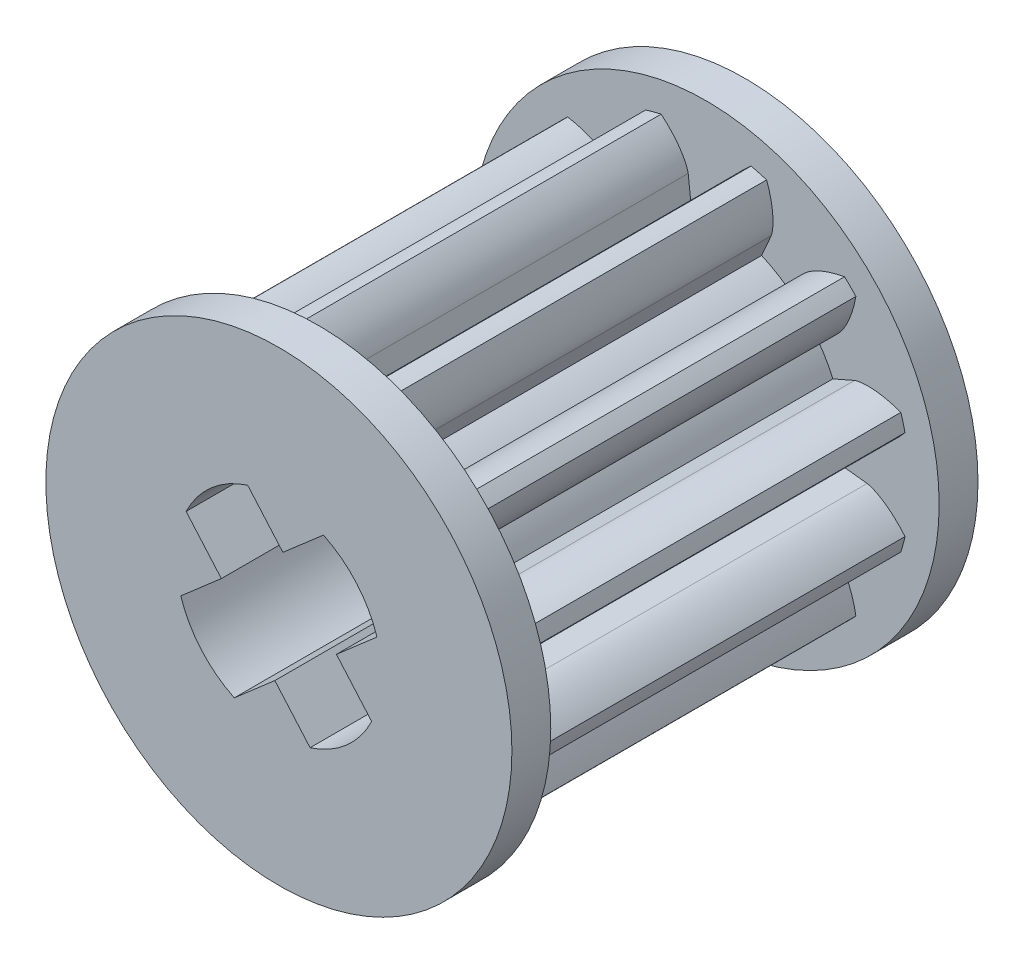
SolidWorks part; units mm, degrees
ref_plane "Front Plane" through (0, 0, 0) normal (0, 0, 1) x (1, 0, 0)
ref_plane "Top Plane" through (0, 0, 0) normal (0, 1, 0) x (1, 0, 0)
ref_plane "Right Plane" through (0, 0, 0) normal (1, 0, 0) x (0, 0, -1)
ref_axis "Axis1" [suppressed] through (0, 0, 71.2135) along (0, 0, -1)
sketch "Sketch1" plane through (0, 0, 0) normal (0, 0, 1) x (1, 0, 0)
  circle A0 centre (0, 0) radius 3.5625
  circle A1 centre (0, 0) radius 4.1723
  circle A2 centre (0, 0) radius 3.75
  circle A3 centre (0, 0) radius 4.5
  circle A4 centre (0, 0) radius 5.25
  dimension "Pitch" = 9
  dimension "Addendum" = 10.5
  dimension "Clearance" = 7.5
  dimension "Base" = 8.3447
  dimension "Root" = 7.125
extrude "Boss-Extrude1" add sketch "Sketch1" along normal blind 10 contours A4
sketch "Sketch3" plane through (0, 0, 0) normal (0, 0, 1) x (1, 0, 0)
  line L0 (0.4615, 4.1467) -> (0, 0) construction
  line L1 (0.7855, 4.0977) -> (0, 0) construction
  line L2 (1.1046, 4.0235) -> (0, 0) construction
  line L3 (1.4168, 3.9244) -> (0, 0) construction
  line L4 (1.7204, 3.8011) -> (0, 0) construction
  line L5 (2.0133, 3.6544) -> (0, 0) construction
  line L6 (2.2938, 3.4852) -> (0, 0) construction
  line L7 (2.5602, 3.2945) -> (0, 0) construction
  line L8 (2.8108, 3.0835) -> (0, 0) construction
  line L9 (3.044, 2.8534) -> (0, 0) construction
  line L10 (3.2585, 2.6058) -> (0, 0) construction
  line L11 (0.7855, 4.0977) -> (0.4636, 4.1594) construction
  line L12 (3.2585, 2.6058) -> (1.2119, 5.1651) construction
  line L13 (1.1046, 4.0235) -> (0.4725, 4.197) construction
  line L14 (1.4168, 3.9244) -> (0.4922, 4.2582) construction
  line L15 (1.7204, 3.8011) -> (0.5262, 4.3416) construction
  line L16 (2.0133, 3.6544) -> (0.5782, 4.4451) construction
  line L17 (2.2938, 3.4852) -> (0.6514, 4.5662) construction
  line L18 (2.5602, 3.2945) -> (0.7489, 4.702) construction
  line L19 (2.8108, 3.0835) -> (0.8734, 4.8495) construction
  line L20 (3.044, 2.8534) -> (1.0271, 5.0051) construction
  line L21 (0, 0) -> (0, 4.5) construction
  line L22 (0, 0) -> (0.5874, 4.4615)
  line L23 (0, 0) -> (-0.5874, 4.4615)
  line L24 (0.4615, 4.1467) -> (0.3941, 3.5406)
  line L25 (-0.4615, 4.1467) -> (-0.3941, 3.5406)
  circle A0 centre (0, 0) radius 4.1723 construction
  circle A1 centre (0, 0) radius 4.5 construction
  arc A2 (3.2585, 2.6058) -> (0.4615, 4.1467) centre (0, 0) ccw construction
  circle A3 centre (0, 0) radius 3.5625 construction
  circle A4 centre (0, 0) radius 3.5625
  circle A5 centre (0, 0) radius 5.25 construction
  circle A6 centre (0, 0) radius 5.25
  spline S0 degree 3 poles (0.4615, 4.1467) (0.464, 4.1637) (0.473, 4.2013) (0.4941, 4.2666) (0.5286, 4.35) (0.6061, 4.5031) (0.722, 4.6743) (0.9298, 4.9199) (1.0915, 5.0686) (1.2119, 5.1651) knots 0 0 0 0 0.040008 0.090018 0.16003 0.250047 0.489907 0.639935 1 1 1 1
  spline S1 degree 3 poles (-0.4615, 4.1467) (-0.464, 4.1637) (-0.473, 4.2013) (-0.4941, 4.2666) (-0.5286, 4.35) (-0.6061, 4.5031) (-0.722, 4.6743) (-0.9298, 4.9199) (-1.0915, 5.0686) (-1.2119, 5.1651) knots 0 0 0 0 0.040008 0.090018 0.16003 0.250047 0.489907 0.639935 1 1 1 1
  point P18 (0, 0)
  dimension "D2" = 45
  dimension "D3" = 0.3277
  dimension "D4" = 3.2769
  dimension "D5" = 0.6554
  dimension "D6" = 0.9831
  dimension "D7" = 1.3108
  dimension "D8" = 1.6385
  dimension "D9" = 1.9662
  dimension "D10" = 2.2939
  dimension "D11" = 2.6216
  dimension "D12" = 2.9492
  dimension "D13" = 15
  dimension "D1" = 11
extrude "Cut-Extrude3" cut sketch "Sketch3" along normal through all contours S1 L25 A4 L24 S0 A6 region at (0, 4.5519, 0)
fillet "Fillet2" [suppressed] radius 0.05
pattern_circular "CirPattern1" count 12 over 360 about axis through (0, 0, 71.2135) along (0, 0, -1) of "Cut-Extrude3", "Fillet2"
ref_plane "Plane2" through (0, 0, 5) normal (0, 0, 1) x (1, 0, 0)
sketch "Sketch6" plane through (0, 0, 10) normal (0, 0, 1) x (1, 0, 0)
  circle A0 centre (0, 0) radius 6
  dimension "D1" = 12
extrude "Boss-Extrude2" add sketch "Sketch6" along normal blind 1
mirror "Mirror1" about plane through (0, 0, 5) normal (0, 0, 1) of "Boss-Extrude2"
sketch "Sketch5" plane through (0, 0, 0) normal (0, 0, 1) x (1, 0, 0)
  line L0 (-0.8803, 2.2327) -> (0.0791, 1.1286) construction
  line L1 (-1.1286, 0.0791) -> (-2.088, 1.1833) construction
  line L2 (-2.2327, -0.8803) -> (-1.1286, 0.0791) construction
  line L3 (-0.0791, -1.1286) -> (-1.1833, -2.088) construction
  line L4 (0.8803, -2.2327) -> (-0.0791, -1.1286) construction
  line L5 (1.1286, -0.0791) -> (2.088, -1.1833) construction
  line L6 (2.2327, 0.8803) -> (1.1286, -0.0791) construction
  line L7 (0.0791, 1.1286) -> (1.1833, 2.088) construction
  line L8 (-0.8803, 2.2327) -> (0.0791, 1.1286)
  line L9 (-1.1286, 0.0791) -> (-2.088, 1.1833)
  line L10 (-2.2327, -0.8803) -> (-1.1286, 0.0791)
  line L11 (-0.0791, -1.1286) -> (-1.1833, -2.088)
  line L12 (0.8803, -2.2327) -> (-0.0791, -1.1286)
  line L13 (1.1286, -0.0791) -> (2.088, -1.1833)
  line L14 (2.2327, 0.8803) -> (1.1286, -0.0791)
  line L15 (0.0791, 1.1286) -> (1.1833, 2.088)
  line L16 (0.1039, 1.4813) -> (1.1479, 2.3885)
  line L17 (-0.8033, 2.5253) -> (0.1039, 1.4813)
  line L18 (-1.4813, 0.1039) -> (-2.3885, 1.1479)
  line L19 (-2.5253, -0.8033) -> (-1.4813, 0.1039)
  line L20 (-0.1039, -1.4813) -> (-1.1479, -2.3885)
  line L21 (0.8033, -2.5253) -> (-0.1039, -1.4813)
  line L22 (1.4813, -0.1039) -> (2.3885, -1.1479)
  line L23 (2.5253, 0.8033) -> (1.4813, -0.1039)
  arc A0 (-0.8803, 2.2327) -> (-2.088, 1.1833) centre (0, 0) ccw construction
  arc A1 (-2.2327, -0.8803) -> (-1.1833, -2.088) centre (0, 0) ccw construction
  arc A2 (0.8803, -2.2327) -> (2.088, -1.1833) centre (0, 0) ccw construction
  arc A3 (2.2327, 0.8803) -> (1.1833, 2.088) centre (0, 0) ccw construction
  arc A4 (-0.8803, 2.2327) -> (-2.088, 1.1833) centre (0, 0) ccw
  arc A5 (-2.2327, -0.8803) -> (-1.1833, -2.088) centre (0, 0) ccw
  arc A6 (0.8803, -2.2327) -> (2.088, -1.1833) centre (0, 0) ccw
  arc A7 (2.2327, 0.8803) -> (1.1833, 2.088) centre (0, 0) ccw
  arc A10 (2.5253, 0.8033) -> (1.1479, 2.3885) centre (0, 0) ccw
  arc A11 (-0.8033, 2.5253) -> (-2.3885, 1.1479) centre (0, 0) ccw
  arc A13 (-2.5253, -0.8033) -> (-1.1479, -2.3885) centre (0, 0) ccw
  arc A14 (0.8033, -2.5253) -> (2.3885, -1.1479) centre (0, 0) ccw
  dimension "D1" = 0.25
extrude "Cut-Extrude4" cut sketch "Sketch5" along normal through all both and the other way through all contours L14 A7 L15 L8 A4 L9 L10 A5 L11 L12 A6 L13 | L21 A14 L22 L23 A10 L16 L17 A11 L18 L19 A13 L20 A7 L14 L13 A6 L12 L11 A5 L10 L9 A4 L8 L15 region at (0, 0, 0) region at (0.6727, 1.881, 0)
equation "\"Module\"= .75"
equation "\"numTeeth\" = 12"
equation "\"pressureAngle\"= 22deg"
equation "\"toothRadius\"= .05"
equation "\"Pitch@Sketch1\"=\"Module\"*\"numTeeth\""
equation "\"Addendum@Sketch1\"=\"Pitch@Sketch1\"+\"Module\"*2"
equation "\"Clearance@Sketch1\"=\"Pitch@Sketch1\"-\"Module\"*2"
equation "\"Base@Sketch1\"=\"Pitch@Sketch1\"*cos(\"pressureAngle\")"
equation "\"Root@Sketch1\"=\"Pitch@Sketch1\"-\"Module\"*1.25*2"
equation "\"D4@Sketch3\"= \"Base@Sketch1\" * pi / 8"
equation "\"D3@Sketch3\"= \"D4@Sketch3\" / 10"
equation "\"D5@Sketch3\"=\"D3@Sketch3\"*2"
equation "\"D6@Sketch3\"=\"D3@Sketch3\"*3"
equation "\"D7@Sketch3\"=\"D3@Sketch3\"*4"
equation "\"D8@Sketch3\"=\"D3@Sketch3\"*5"
equation "\"D9@Sketch3\"=\"D3@Sketch3\"*6"
equation "\"D10@Sketch3\"=\"D3@Sketch3\"*7"
equation "\"D11@Sketch3\"=\"D3@Sketch3\"*8"
equation "\"D12@Sketch3\"=\"D3@Sketch3\"*9"
equation "\"D13@Sketch3\"=180/\"numTeeth\""
equation "\"D1@CirPattern1\"=\"numTeeth\""
equation "\"D1@Fillet2\"= \"toothRadius\""
